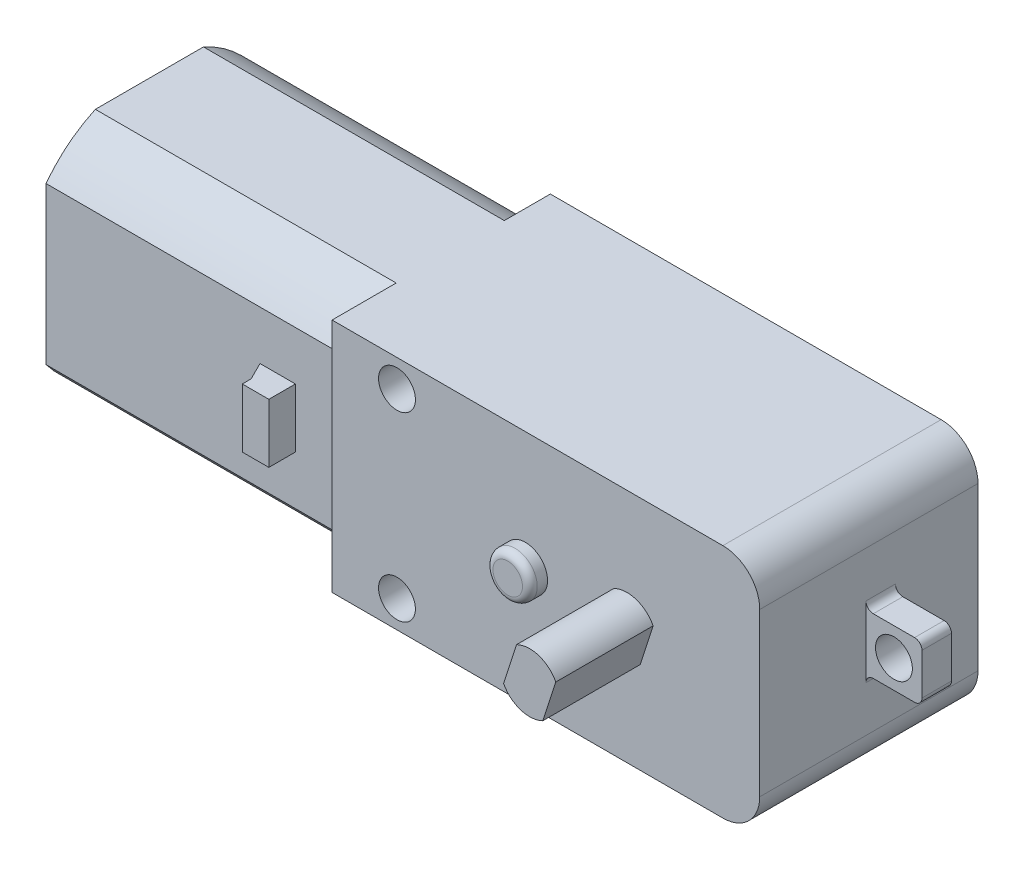
SolidWorks part; units mm, degrees
ref_plane "Front Plane" through (0, 0, 0) normal (0, 0, 1) x (1, 0, 0)
ref_plane "Top Plane" through (0, 0, 0) normal (0, 1, 0) x (1, 0, 0)
ref_plane "Right Plane" through (0, 0, 0) normal (1, 0, 0) x (0, 0, -1)
sketch "Sketch1" plane through (0, 0, 0) normal (0, 0, 1) x (1, 0, 0)
  line L1 (0, -10.16) -> (36.83, -10.16)
  line L2 (0, -10.16) -> (0, 10.16)
  line L3 (0, 10.16) -> (36.83, 10.16)
  line L4 (36.83, -10.16) -> (36.83, 10.16)
  point P4 (0, 0)
  dimension "D1" = 36.83
  dimension "D2" = 20.32
extrude "Boss-Extrude1" add sketch "Sketch1" along normal blind 18.796
fillet "Fillet1" radius 3.175 2 edges at (36.83, 10.16, 9.398) (36.83, -10.16, 9.398)
sketch "Sketch2" plane through (0, 0, 0) normal (-1, 0, 0) x (0, 0, 1)
  line L0 (0, 7.112) -> (0, -7.112)
  line L1 (0, 10.16) -> (0, -10.16) construction
  line L2 (17.526, -6.7531) -> (17.526, 6.7531)
  line L3 (18.796, 10.16) -> (18.796, -10.16) construction
  line L6 (0, 10.16) -> (0, -10.16)
  line L7 (0, -10.16) -> (18.796, -10.16)
  line L8 (18.796, -10.16) -> (18.796, 10.16)
  line L9 (18.796, 10.16) -> (0, 10.16)
  line L10 (0, 7.112) -> (0, -7.112)
  line L11 (3.9651, -10.16) -> (13.2769, -10.16)
  line L13 (13.2769, 10.16) -> (3.9651, 10.16)
  arc A0 (3.9651, 10.16) -> (0, 7.112) centre (8.621, 0) ccw
  arc A1 (13.2769, -10.16) -> (17.526, -6.7531) centre (8.621, 0) ccw
  arc A2 (0, -7.112) -> (3.9651, -10.16) centre (8.621, 0) ccw
  arc A3 (17.526, 6.7531) -> (13.2769, 10.16) centre (8.621, 0) ccw
  line M3 (0, 10.16) -> (0, -10.16)
  line M4 (0, -10.16) -> (18.796, -10.16)
  line M6 (18.796, 10.16) -> (0, 10.16)
  dimension "D1" = 22.352
  dimension "D2" = 14.224
  dimension "D4" = 1.27
  dimension "D3" = 0
extrude "Boss-Extrude2" add sketch "Sketch2" along normal blind 25.908 contours L2 A3 A0 A2 A1 M6 M3 M4 region at (0, 0, 8.7244)
sketch "Sketch3" plane through (0, 0, 18.796) normal (0, 0, 1) x (1, 0, 0)
  line L0 (36.83, -6.985) -> (36.83, 6.985) construction
  line L1 (23.7085, 0.5477) -> (27.0915, -0.5477) construction
  line L2 (24.2673, 2.2734) -> (23.1497, -1.178)
  line L3 (27.6503, 1.178) -> (26.5327, -2.2734)
  arc A0 (23.1497, -1.178) -> (26.5327, -2.2734) centre (25.4, 0) ccw
  arc A1 (27.6503, 1.178) -> (24.2673, 2.2734) centre (25.4, 0) ccw
  point P7 (25.4, 0)
  dimension "D2" = 5.08
  dimension "D1" = 11.43
  dimension "D3" = 3.556
extrude "Boss-Extrude3" add sketch "Sketch3" along normal blind 8.382
sketch "Sketch4" plane through (0, 0, 18.796) normal (0, 0, 1) x (1, 0, 0)
  line L0 (14.9479, 0) -> (-14.9479, 0) construction
  line L1 (0, 10.16) -> (0, -10.16) construction
  line L2 (33.655, 10.16) -> (0, 10.16) construction
  circle A0 centre (5.588, 7.8105) radius 1.5875
  circle A1 centre (5.588, -7.8105) radius 1.5875
  point P6 (3.7792, 6.6379)
  point P9 (0, 0)
  point P11 (7.2997, 7.4965)
  dimension "D1" = 3.175
  dimension "D2" = 5.588
  dimension "D3" = 2.3495
extrude "Cut-Extrude1" cut sketch "Sketch4" against normal through all
sketch "Sketch5" plane through (0, 0, 0) normal (0, 0, -1) x (-1, 0, 0)
  line L0 (-36.83, -6.985) -> (-36.83, 6.985) construction
  line L1 (-36.83, 2.413) -> (-41.656, 2.413)
  line L2 (-36.83, 2.413) -> (-36.83, -2.413)
  line L3 (-36.83, -2.413) -> (-41.656, -2.413)
  line L4 (-41.656, 2.413) -> (-41.656, -2.413)
  line L5 (-36.83, -6.985) -> (-36.83, 6.985)
  circle A0 centre (-39.243, 0) radius 1.5875
  point P8 (-36.83, 0)
  point P9 (-36.83, 0)
  point P10 (0, 0)
  point P11 (-41.656, 0)
  point P12 (-39.243, 2.413)
  line M10 (-36.83, 6.985) -> (-36.83, -6.985)
  dimension "D3" = 3.175
  dimension "D1" = 4.826
  dimension "D2" = 4.826
extrude "Boss-Extrude4" add sketch "Sketch5" against normal blind 2.54 from offset 7.112 contours L1 L4 L3 A0 M10 region at (36.8982, 0, 0) offset against normal yes
fillet "Fillet2" radius 0.635 4 edges at (36.83, 2.413, 8.382) (36.83, -2.413, 8.382) (41.656, 2.413, 8.382) (41.656, -2.413, 8.382)
ref_plane "Plane1" through (0, 0, 0) normal (0, -1, 0) x (-1, 0, 0)
ref_plane "Plane2" through (0, 0, 8.763) normal (0, 0, -1) x (-1, 0, 0)
sketch "Sketch6" plane through (0, 0, 0) normal (0, -1, 0) x (-1, 0, 0)
  line L1 (25.908, 0) -> (0, 0) construction
  line L6 (17.526, 0) -> (18.796, 1.27)
  line L7 (18.796, 1.27) -> (25.908, 1.27)
  line L8 (25.908, 1.27) -> (25.908, 0)
  line L9 (25.908, 0) -> (17.526, 0)
  line L10 (11.176, -8.763) -> (-11.176, -8.763) construction
  line L16 (4.431, -19.812) -> (6.717, -19.812)
  line L17 (4.431, -17.526) -> (4.431, -19.812)
  line L18 (7.479, -17.526) -> (4.431, -17.526)
  line L19 (6.717, 2.286) -> (6.717, 1.524)
  line L20 (4.431, 2.286) -> (6.717, 2.286)
  line L21 (4.431, 0) -> (4.431, 2.286)
  line L22 (7.479, 0) -> (4.431, 0)
  line L23 (6.717, 1.524) -> (7.479, 0)
  line L24 (0, -3.9651) -> (0, 0) construction
  line L25 (6.717, -19.05) -> (7.479, -17.526)
  line L26 (6.717, -19.812) -> (6.717, -19.05)
  point P5 (0, 0)
  dimension "D1" = 2.286
  dimension "D2" = 2.286
  dimension "D3" = 0.762
  dimension "D4" = 3.048
  dimension "D5" = 4.431
  dimension "D6" = 8.382
  dimension "D7" = 1.27
  dimension "D8" = 7.112
extrude "Boss-Extrude5" add sketch "Sketch6" along normal mid plane 5.08 contours L20 L19 L23 L22 L21 | L16 L26 L25 L18 L17
extrude "Boss-Extrude6" add sketch "Sketch6<3>" along normal mid plane 8.128 contours L7 L8 L9 L6
sketch "Sketch6<3>" plane through (0, 0, 0) normal (0, -1, 0) x (-1, 0, 0) same geometry as "Sketch6"
fillet "Fillet3" radius 1.27 2 edges at (-25.908, 0, -1.27) (-18.796, 0, -1.27)
sketch "Sketch8" plane through (0, 0, 18.796) normal (0, 0, 1) x (1, 0, 0)
  line L0 (-10.3378, 0) -> (10.3378, 0) construction
  line L1 (-6.717, -2.54) -> (-6.717, 2.54) construction
  circle A0 centre (16.651, 0) radius 1.905
  dimension "D1" = 3.81
  dimension "D2" = 23.368
extrude "Boss-Extrude7" add sketch "Sketch8" along normal blind 1.524
fillet "Fillet4" radius 0.635 1 edges at (18.556, 0, 20.32)
